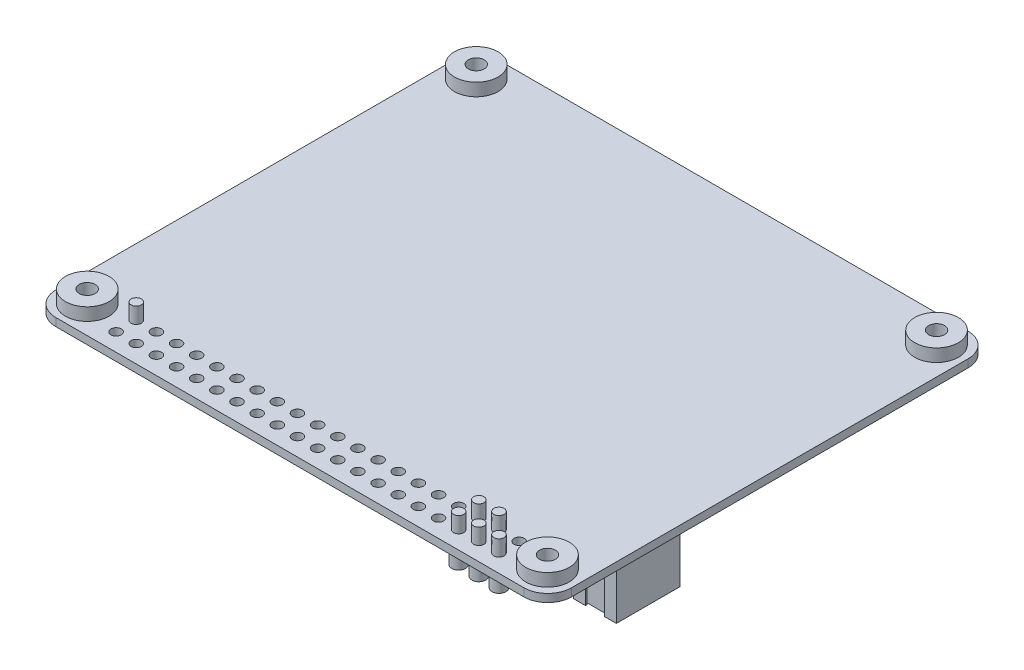
SolidWorks part; units mm, degrees
ref_plane "前视基准面" through (0, 0, 0) normal (0, 0, 1) x (1, 0, 0)
ref_plane "上视基准面" through (0, 0, 0) normal (0, 1, 0) x (1, 0, 0)
ref_plane "右视基准面" through (0, 0, 0) normal (1, 0, 0) x (0, 0, -1)
sketch "草图1" plane through (0, 0, 0) normal (0, 1, 0) x (1, 0, 0)
  line L1 (32.5, -28) -> (-32.5, -28)
  line L2 (32.5, -28) -> (32.5, 28)
  line L3 (32.5, 28) -> (-32.5, 28)
  line L4 (-32.5, -28) -> (-32.5, 28)
  line L5 (32.5, -28) -> (-32.5, 28) construction
  line L6 (32.5, 28) -> (-32.5, -28) construction
  point P0 (0, 0)
  dimension "D1" = 56
  dimension "D2" = 65
extrude "凸台-拉伸1" add sketch "草图1" along normal blind 1
fillet "圆角1" radius 3 4 edges at (32.5, 0.5, -28) (32.5, 0.5, 28) (-32.5, 0.5, 28) (-32.5, 0.5, -28)
sketch "草图2" plane through (0, 1, 0) normal (0, 1, 0) x (1, 0, 0)
  circle A0 centre (-29.0307, 24.5287) radius 2.75
  circle A1 centre (28.9808, 24.5287) radius 2.75
  circle A2 centre (-29.0307, -24.5065) radius 2.75
  circle A3 centre (28.9808, -24.5065) radius 2.75
  dimension "D1" = 5.5
extrude "凸台-拉伸2" add sketch "草图2" along normal blind 1.6
sketch "草图3" plane through (0, 2.6, 0) normal (0, 1, 0) x (1, 0, 0)
  circle A0 centre (-29.0307, 24.5287) radius 1
  circle A1 centre (28.9808, 24.5287) radius 1
  circle A2 centre (-29.0307, -24.5065) radius 1
  circle A3 centre (28.9808, -24.5065) radius 1
  dimension "D1" = 2
extrude "切除-拉伸1" cut sketch "草图3" against normal up to next
sketch "草图4" plane through (0, 0, 0) normal (0, -1, 0) x (1, 0, 0)
  line L0 (29.5, -28) -> (-29.5, -28) construction
  line L1 (25.5, -28) -> (16.5, -28)
  line L2 (25.5, -28) -> (25.5, -20.6)
  line L3 (25.5, -20.6) -> (16.5, -20.6)
  line L4 (16.5, -28) -> (16.5, -20.6)
  line L5 (32.5, 25) -> (32.5, -25) construction
  dimension "D1" = 7.4
  dimension "D2" = 9
  dimension "D3" = 7
extrude "凸台-拉伸3" add sketch "草图4" along normal blind 3.2
sketch "草图5" plane through (0, 0, -28) normal (0, 0, -1) x (-1, 0, 0)
  line L0 (-29.5, 0) -> (-25.5, 0) construction
  line L1 (-16.5, -3.2) -> (-25.5, -3.2)
  line L2 (-16.5, -3.2) -> (-16.5, 0)
  line L3 (-16.5, 0) -> (-25.5, 0)
  line L4 (-25.5, -3.2) -> (-25.5, 0)
  line L5 (-25.5, -3.2) -> (-25.5, 0) construction
extrude "凸台-拉伸4" add sketch "草图5" along normal blind 1
fillet "圆角3" radius 1 4 edges at (25.5, 0, -28.5) (25.5, -3.2, -24.8) (16.5, -3.2, -24.8) (16.5, 0, -28.5)
sketch "草图6" plane through (0, 0, 0) normal (0, -1, 0) x (1, 0, 0)
  line L0 (-32.5, -25) -> (-32.5, 25) construction
  circle A0 centre (-17.5, 0) radius 7
  dimension "D1" = 14
  dimension "D2" = 15
extrude "凸台-拉伸5" add sketch "草图6" along normal blind 2
sketch "草图8" plane through (0, 0, 0) normal (0, -1, 0) x (1, 0, 0)
  circle A0 centre (28.9808, 24.5065) radius 2
  circle A1 centre (28.9808, -24.5287) radius 2
  circle A2 centre (-29.0307, -24.5287) radius 2
  circle A3 centre (-29.0307, 24.5065) radius 2
  dimension "D1" = 4
extrude "凸台-拉伸6" add sketch "草图8" along normal blind 0.5
sketch "草图9" plane through (0, 0, 0) normal (0, 1, 0) x (1, 0, 0)
  circle A0 centre (-29.0307, 24.5287) radius 1
  circle A1 centre (28.9808, 24.5287) radius 1
  circle A2 centre (-29.0307, -24.5065) radius 1
  circle A3 centre (28.9808, -24.5065) radius 1
  circle A4 centre (28.9808, -24.5065) radius 2 construction
  circle A5 centre (28.9808, 24.5287) radius 2 construction
  circle A6 centre (-29.0307, -24.5065) radius 2 construction
  circle A7 centre (-29.0307, 24.5287) radius 2 construction
extrude "切除-拉伸2" cut sketch "草图9" against normal up to next
sketch "草图10" plane through (0, 0, -29) normal (0, 0, -1) x (-1, 0, 0)
  line L8 (-17.5, -0.2) -> (-24.5, -0.2)
  line L9 (-25.3, -1) -> (-25.3, -2.2)
  line L10 (-24.5, -3) -> (-17.5, -3)
  line L11 (-16.7, -2.2) -> (-16.7, -1)
  line L12 (-17.5, -0.2) -> (-24.5, -0.2)
  line L13 (-25.3, -1) -> (-25.3, -2.2)
  line L14 (-24.5, -3) -> (-17.5, -3)
  line L15 (-16.7, -2.2) -> (-16.7, -1)
  arc A8 (-24.5, -0.2) -> (-25.3, -1) centre (-24.5, -1) ccw
  arc A9 (-25.3, -2.2) -> (-24.5, -3) centre (-24.5, -2.2) ccw
  arc A10 (-17.5, -3) -> (-16.7, -2.2) centre (-17.5, -2.2) ccw
  arc A11 (-16.7, -1) -> (-17.5, -0.2) centre (-17.5, -1) ccw
  arc A12 (-24.5, -0.2) -> (-25.3, -1) centre (-24.5, -1) ccw
  arc A13 (-25.3, -2.2) -> (-24.5, -3) centre (-24.5, -2.2) ccw
  arc A14 (-17.5, -3) -> (-16.7, -2.2) centre (-17.5, -2.2) ccw
  arc A15 (-16.7, -1) -> (-17.5, -0.2) centre (-17.5, -1) ccw
  dimension "D1" = 0.2
extrude "切除-拉伸3" cut sketch "草图10" against normal blind 8
sketch "草图11" plane through (0, 0, 0) normal (0, -1, 0) x (1, 0, 0)
  line L0 (16.5, -28) -> (-29.5, -28) construction
  line L1 (6, -27.8) -> (10.5, -27.8)
  line L2 (6, -27.8) -> (6, -26.3)
  line L3 (6, -26.3) -> (10.5, -26.3)
  line L4 (10.5, -27.8) -> (10.5, -26.3)
  line L5 (16.5, -20.6) -> (16.5, -28) construction
  line L6 (-2.6793, -27.2) -> (-9.3793, -27.2)
  line L7 (-2.6793, -27.2) -> (-2.6793, -25)
  line L8 (-2.6793, -25) -> (-9.3793, -25)
  line L9 (-9.3793, -27.2) -> (-9.3793, -25)
  dimension "D1" = 6
  dimension "D2" = 4.5
  dimension "D3" = 6.7
  dimension "D4" = 0.8
  dimension "D5" = 2.2
  dimension "D6" = 1.5
  dimension "D7" = 8.7
  dimension "D8" = 0.2
extrude "凸台-拉伸7" add sketch "草图11" along normal blind 1.5
sketch "草图12" plane through (0, 0, 0) normal (0, -1, 0) x (1, 0, 0)
  line L0 (16.5, -28) -> (-29.5, -28) construction
  line L1 (-16.6, -28) -> (-23.9, -28)
  line L2 (-16.6, -28) -> (-16.6, -22.7)
  line L3 (-16.6, -22.7) -> (-23.9, -22.7)
  line L4 (-23.9, -28) -> (-23.9, -22.7)
  line L5 (-32.5, -25) -> (-32.5, 25) construction
  dimension "D1" = 7.3
  dimension "D2" = 8.6
  dimension "D3" = 5.3
extrude "凸台-拉伸8" add sketch "草图12" along normal blind 2.4
sketch "草图13" plane through (0, 0, -28) normal (0, 0, -1) x (-1, 0, 0)
  line L1 (23.9, -2.4) -> (16.6, -2.4)
  line L2 (23.9, -2.4) -> (23.9, 0)
  line L3 (23.9, 0) -> (16.6, 0)
  line L4 (16.6, -2.4) -> (16.6, 0)
extrude "凸台-拉伸9" add sketch "草图13" along normal up to surface (1 mm away) up to face at (21, -1.6, -29)
chamfer "倒角1" distance 0.4 angle 45 2 edges at (-16.6, -2.4, -25.85) (-23.9, -2.4, -25.85)
chamfer "倒角2" distance 1 angle 45 2 edges at (-16.6, 0, -28.5) (-23.9, 0, -28.5)
sketch "草图14" plane through (0, 0, -29) normal (0, 0, -1) x (-1, 0, 0)
  line L16 (22.8172, -0.2) -> (17.6828, -0.2)
  line L17 (17.6828, -0.2) -> (16.8, -1.0828)
  line L18 (16.8, -1.0828) -> (16.8, -1.9172)
  line L19 (16.8, -1.9172) -> (17.0828, -2.2)
  line L20 (17.0828, -2.2) -> (23.4172, -2.2)
  line L21 (23.4172, -2.2) -> (23.7, -1.9172)
  line L22 (23.7, -1.9172) -> (23.7, -1.0828)
  line L23 (23.7, -1.0828) -> (22.8172, -0.2)
  line L24 (22.8172, -0.2) -> (17.6828, -0.2)
  line L25 (17.6828, -0.2) -> (16.8, -1.0828)
  line L26 (16.8, -1.0828) -> (16.8, -1.9172)
  line L27 (16.8, -1.9172) -> (17.0828, -2.2)
  line L28 (17.0828, -2.2) -> (23.4172, -2.2)
  line L29 (23.4172, -2.2) -> (23.7, -1.9172)
  line L30 (23.7, -1.9172) -> (23.7, -1.0828)
  line L31 (23.7, -1.0828) -> (22.8172, -0.2)
  dimension "D1" = 0.2
extrude "切除-拉伸4" cut sketch "草图14" against normal blind 2.4
sketch "草图15" plane through (0, 0, -27.2) normal (0, 0, -1) x (-1, 0, 0)
  line L1 (6.6577, -1.3336) -> (5.7436, -1.3336)
  line L2 (6.6577, -1.3336) -> (6.6577, -0.2043)
  line L3 (6.6577, -0.2043) -> (5.7436, -0.2043)
  line L4 (5.7436, -1.3336) -> (5.7436, -0.2043)
extrude "凸台-拉伸10" add sketch "草图15" along normal blind 0.8
sketch "草图16" plane through (0, 0, -27.8) normal (0, 0, -1) x (-1, 0, 0)
  line L1 (-6.8432, -1.3088) -> (-8.9595, -1.3088)
  line L2 (-6.8432, -1.3088) -> (-6.8432, -0.1641)
  line L3 (-6.8432, -0.1641) -> (-8.9595, -0.1641)
  line L4 (-8.9595, -1.3088) -> (-8.9595, -0.1641)
extrude "凸台-拉伸11" add sketch "草图16" along normal blind 0.5
sketch "草图17" plane through (0, 0, -28) normal (0, 0, -1) x (-1, 0, 0)
  line L0 (23.9, -1) -> (23.9, 0)
  line L1 (23.9, 0) -> (22.9, 0)
  line L2 (22.9, 0) -> (23.9, -1)
  line L3 (16.6, 0) -> (17.6, 0)
  line L4 (17.6, 0) -> (16.6, -1)
  line L5 (16.6, -1) -> (16.6, 0) construction
  line L6 (16.6, -1) -> (16.6, 0)
extrude "切除-拉伸5" cut sketch "草图17" against normal up to surface (5.3 mm away) up to face at (-20.25, -1.4667, -22.7)
fillet "圆角4" radius 0.2 1 edges at (-17.5, -2, -7)
sketch "草图18" plane through (0, 0, 0) normal (0, -1, 0) x (1, 0, 0)
  line L0 (-29.5, 28) -> (29.5, 28) construction
  line L1 (27.1, 8.3) -> (20.1, 8.3)
  line L2 (27.1, 8.3) -> (27.1, 1.3)
  line L3 (27.1, 1.3) -> (20.1, 1.3)
  line L4 (20.1, 8.3) -> (20.1, 1.3)
  line L5 (27.1, -3.4) -> (20.1, -3.4)
  line L6 (27.1, -3.4) -> (27.1, -10.4)
  line L7 (27.1, -10.4) -> (20.1, -10.4)
  line L8 (20.1, -3.4) -> (20.1, -10.4)
  line L9 (32.5, 25) -> (32.5, -25) construction
  dimension "D1" = 7
  dimension "D2" = 19.7
  dimension "D3" = 4.7
  dimension "D4" = 5.4
extrude "凸台-拉伸12" add sketch "草图18" along normal blind 3
sketch "草图19" plane through (0, 0, 0) normal (0, -1, 0) x (1, 0, 0)
  line L0 (32.5, 25) -> (32.5, -25) construction
  line L1 (32, 18.85) -> (26.6, 18.85)
  line L2 (32, 18.85) -> (32, 10.85)
  line L3 (32, 10.85) -> (26.6, 10.85)
  line L4 (26.6, 18.85) -> (26.6, 10.85)
  line L5 (-29.5, 28) -> (29.5, 28) construction
  dimension "D1" = 8
  dimension "D2" = 5.4
  dimension "D3" = 0.5
  dimension "D4" = 9.15
extrude "凸台-拉伸13" add sketch "草图19" along normal blind 6.22
sketch "草图20" plane through (0, -6.22, 0) normal (0, -1, 0) x (1, 0, 0)
  line L0 (30.5, 18.85) -> (30.5, 18.65)
  line L1 (32, 18.85) -> (26.6, 18.85) construction
  line L2 (30.5, 18.65) -> (31.3599, 18.65)
  line L3 (31.3599, 18.65) -> (31.3599, 18.45)
  line L4 (31.3599, 18.45) -> (26.9378, 18.45)
  line L5 (26.9378, 18.45) -> (26.9378, 18.65)
  line L6 (26.9378, 18.65) -> (28.1, 18.65)
  line L7 (28.1, 18.65) -> (28.1, 18.85)
  line L8 (32, 18.85) -> (26.6, 18.85) construction
  line L9 (28.1, 18.85) -> (30.5, 18.85)
  line L10 (30.5, 10.85) -> (30.5, 11.05)
  line L11 (26.6, 10.85) -> (32, 10.85) construction
  line L12 (30.5, 11.05) -> (31.3599, 11.05)
  line L13 (31.3599, 11.05) -> (31.3599, 11.25)
  line L14 (31.3599, 11.25) -> (26.9378, 11.25)
  line L15 (26.9378, 11.25) -> (26.9378, 11.05)
  line L16 (26.9378, 11.05) -> (28.1, 11.05)
  line L17 (28.1, 11.05) -> (28.1, 10.85)
  line L18 (28.1, 10.85) -> (30.5, 10.85)
  line L19 (32, 10.85) -> (32, 18.85) construction
  line L20 (26.6, 18.85) -> (26.6, 10.85) construction
  dimension "D1" = 0.2
  dimension "D2" = 0.2
  dimension "D3" = 0.2
  dimension "D4" = 1.5
  dimension "D5" = 1.5
extrude "切除-拉伸6" cut sketch "草图20" against normal blind 6.22
sketch "草图21" plane through (0, -6.22, 0) normal (0, -1, 0) x (1, 0, 0)
  line L1 (31.3599, 18.0753) -> (26.9378, 18.0753)
  line L2 (31.3599, 18.0753) -> (31.3599, 11.6247)
  line L3 (31.3599, 11.6247) -> (26.9378, 11.6247)
  line L4 (26.9378, 18.0753) -> (26.9378, 11.6247)
  line L5 (31.3599, 18.0753) -> (26.9378, 11.6247) construction
  line L6 (31.3599, 11.6247) -> (26.9378, 18.0753) construction
  point P0 (29.1489, 14.85)
extrude "切除-拉伸7" cut sketch "草图21" against normal blind 5
sketch "草图22" plane through (0, -1.22, 0) normal (0, -1, 0) x (1, 0, 0)
  line L1 (29.5742, 16.0721) -> (29.0742, 16.0721)
  line L2 (29.5742, 16.0721) -> (29.5742, 15.5721)
  line L3 (29.5742, 15.5721) -> (29.0742, 15.5721)
  line L4 (29.0742, 16.0721) -> (29.0742, 15.5721)
  line L5 (29.5742, 16.0721) -> (29.0742, 15.5721) construction
  line L6 (29.5742, 15.5721) -> (29.0742, 16.0721) construction
  line L7 (29.5566, 14.331) -> (29.0566, 14.331)
  line L8 (29.5566, 14.331) -> (29.5566, 13.831)
  line L9 (29.5566, 13.831) -> (29.0566, 13.831)
  line L10 (29.0566, 14.331) -> (29.0566, 13.831)
  line L11 (29.5566, 14.331) -> (29.0566, 13.831) construction
  line L12 (29.5566, 13.831) -> (29.0566, 14.331) construction
  point P0 (29.3242, 15.8221)
  point P5 (29.3066, 14.081)
  dimension "D1" = 0.5
extrude "凸台-拉伸14" add sketch "草图22" along normal blind 5
chamfer "倒角3" distance 0.1 angle 45 8 edges at (29.3066, -6.22, 14.331) (29.5566, -6.22, 14.081) (29.3066, -6.22, 13.831) (29.0566, -6.22, 14.081) (29.3242, -6.22, 16.0721) (29.5742, -6.22, 15.8221) (29.3242, -6.22, 15.5721) (29.0742, -6.22, 15.8221)
sketch "草图23" plane through (0, 0, 0) normal (0, -1, 0) x (1, 0, 0)
  circle A0 centre (12.8757, -15.76) radius 3.3198
extrude "凸台-拉伸15" add sketch "草图23" along normal blind 1.5
sketch "草图24" plane through (0, 0, 0) normal (0, -1, 0) x (1, 0, 0)
  line L1 (18.7716, 11.9855) -> (16.6907, 11.9855)
  line L2 (18.7716, 11.9855) -> (18.7716, 7.4768)
  line L3 (18.7716, 7.4768) -> (16.6907, 7.4768)
  line L4 (16.6907, 11.9855) -> (16.6907, 7.4768)
  line L5 (18.7716, 11.9855) -> (16.6907, 7.4768) construction
  line L6 (18.7716, 7.4768) -> (16.6907, 11.9855) construction
  line L7 (18.7716, 5.3092) -> (16.6907, 5.3092)
  line L8 (18.7716, 5.3092) -> (18.7716, 0.974)
  line L9 (18.7716, 0.974) -> (16.6907, 0.974)
  line L10 (16.6907, 5.3092) -> (16.6907, 0.974)
  line L11 (18.7716, 5.3092) -> (16.6907, 0.974) construction
  line L12 (18.7716, 0.974) -> (16.6907, 5.3092) construction
  line L13 (15.6772, -1.762) -> (10.6483, -1.762)
  line L14 (15.6772, -1.762) -> (15.6772, -7.762)
  line L15 (15.6772, -7.762) -> (10.6483, -7.762)
  line L16 (10.6483, -1.762) -> (10.6483, -7.762)
  line L17 (15.6772, -1.762) -> (10.6483, -7.762) construction
  line L18 (15.6772, -7.762) -> (10.6483, -1.762) construction
  point P0 (17.7311, 9.7312)
  point P5 (17.7311, 3.1416)
  point P10 (13.1628, -4.762)
  dimension "D1" = 6
extrude "凸台-拉伸16" add sketch "草图24" along normal blind 1.5
sketch "草图25" plane through (0, 0, 0) normal (0, -1, 0) x (1, 0, 0)
  line L1 (15.1967, 7.9079) -> (11.1314, 7.9079)
  line L2 (15.1967, 7.9079) -> (15.1967, 3.8427)
  line L3 (15.1967, 3.8427) -> (11.1314, 3.8427)
  line L4 (11.1314, 7.9079) -> (11.1314, 3.8427)
  line L5 (15.1967, 7.9079) -> (11.1314, 3.8427) construction
  line L6 (15.1967, 3.8427) -> (11.1314, 7.9079) construction
  line L7 (21.5006, 15.4932) -> (19.7006, 15.4932)
  line L8 (21.5006, 15.4932) -> (21.5006, 14.4025)
  line L9 (21.5006, 14.4025) -> (19.7006, 14.4025)
  line L10 (19.7006, 15.4932) -> (19.7006, 14.4025)
  line L11 (21.5006, 15.4932) -> (19.7006, 14.4025) construction
  line L12 (21.5006, 14.4025) -> (19.7006, 15.4932) construction
  line L13 (21.5006, 13.6588) -> (19.7006, 13.6588)
  line L14 (21.5006, 13.6588) -> (21.5006, 12.5682)
  line L15 (21.5006, 12.5682) -> (19.7006, 12.5682)
  line L16 (19.7006, 13.6588) -> (19.7006, 12.5682)
  line L17 (21.5006, 13.6588) -> (19.7006, 12.5682) construction
  line L18 (21.5006, 12.5682) -> (19.7006, 13.6588) construction
  line L19 (21.5006, 11.8741) -> (19.7006, 11.8741)
  line L20 (21.5006, 11.8741) -> (21.5006, 10.7834)
  line L21 (21.5006, 10.7834) -> (19.7006, 10.7834)
  line L22 (19.7006, 11.8741) -> (19.7006, 10.7834)
  line L23 (21.5006, 11.8741) -> (19.7006, 10.7834) construction
  line L24 (21.5006, 10.7834) -> (19.7006, 11.8741) construction
  line L25 (18.7662, 14.8563) -> (17.6756, 14.8563)
  line L26 (18.7662, 14.8563) -> (18.7662, 13.0563)
  line L27 (18.7662, 13.0563) -> (17.6756, 13.0563)
  line L28 (17.6756, 14.8563) -> (17.6756, 13.0563)
  line L29 (18.7662, 14.8563) -> (17.6756, 13.0563) construction
  line L30 (18.7662, 13.0563) -> (17.6756, 14.8563) construction
  line L31 (16.9319, 14.8563) -> (15.8412, 14.8563)
  line L32 (16.9319, 14.8563) -> (16.9319, 13.0563)
  line L33 (16.9319, 13.0563) -> (15.8412, 13.0563)
  line L34 (15.8412, 14.8563) -> (15.8412, 13.0563)
  line L35 (16.9319, 14.8563) -> (15.8412, 13.0563) construction
  line L36 (16.9319, 13.0563) -> (15.8412, 14.8563) construction
  line L37 (15.0976, 14.8563) -> (14.0069, 14.8563)
  line L38 (15.0976, 14.8563) -> (15.0976, 13.0563)
  line L39 (15.0976, 13.0563) -> (14.0069, 13.0563)
  line L40 (14.0069, 14.8563) -> (14.0069, 13.0563)
  line L41 (15.0976, 14.8563) -> (14.0069, 13.0563) construction
  line L42 (15.0976, 13.0563) -> (14.0069, 14.8563) construction
  line L43 (13.2632, 14.8563) -> (12.1725, 14.8563)
  line L44 (13.2632, 14.8563) -> (13.2632, 13.0563)
  line L45 (13.2632, 13.0563) -> (12.1725, 13.0563)
  line L46 (12.1725, 14.8563) -> (12.1725, 13.0563)
  line L47 (13.2632, 14.8563) -> (12.1725, 13.0563) construction
  line L48 (13.2632, 13.0563) -> (12.1725, 14.8563) construction
  line L49 (11.3297, 14.8563) -> (10.2391, 14.8563)
  line L50 (11.3297, 14.8563) -> (11.3297, 13.0563)
  line L51 (11.3297, 13.0563) -> (10.2391, 13.0563)
  line L52 (10.2391, 14.8563) -> (10.2391, 13.0563)
  line L53 (11.3297, 14.8563) -> (10.2391, 13.0563) construction
  line L54 (11.3297, 13.0563) -> (10.2391, 14.8563) construction
  line L55 (9.2971, 14.8563) -> (8.2064, 14.8563)
  line L56 (9.2971, 14.8563) -> (9.2971, 13.0563)
  line L57 (9.2971, 13.0563) -> (8.2064, 13.0563)
  line L58 (8.2064, 14.8563) -> (8.2064, 13.0563)
  line L59 (9.2971, 14.8563) -> (8.2064, 13.0563) construction
  line L60 (9.2971, 13.0563) -> (8.2064, 14.8563) construction
  point P0 (13.1641, 5.8753)
  point P5 (20.6006, 14.9478)
  point P10 (20.6006, 13.1135)
  point P15 (20.6006, 11.3287)
  point P20 (18.2209, 13.9563)
  point P25 (16.3866, 13.9563)
  point P30 (14.5522, 13.9563)
  point P35 (12.7179, 13.9563)
  point P40 (10.7844, 13.9563)
  point P45 (8.7518, 13.9563)
  dimension "D1" = 1.8
extrude "凸台-拉伸17" add sketch "草图25" along normal blind 1
sketch "草图26" plane through (0, 0, 0) normal (0, -1, 0) x (1, 0, 0)
  circle A0 centre (24.13, 25.77) radius 0.65
  circle A40 centre (21.59, 25.77) radius 0.65
  circle A41 centre (19.05, 25.77) radius 0.65
  circle A42 centre (16.51, 25.77) radius 0.65
  circle A43 centre (13.97, 25.77) radius 0.65
  circle A44 centre (11.43, 25.77) radius 0.65
  circle A45 centre (8.89, 25.77) radius 0.65
  circle A46 centre (6.35, 25.77) radius 0.65
  circle A47 centre (3.81, 25.77) radius 0.65
  circle A48 centre (1.27, 25.77) radius 0.65
  circle A49 centre (-1.27, 25.77) radius 0.65
  circle A50 centre (-3.81, 25.77) radius 0.65
  circle A51 centre (-6.35, 25.77) radius 0.65
  circle A52 centre (-8.89, 25.77) radius 0.65
  circle A53 centre (-11.43, 25.77) radius 0.65
  circle A54 centre (-13.97, 25.77) radius 0.65
  circle A55 centre (-16.51, 25.77) radius 0.65
  circle A56 centre (-19.05, 25.77) radius 0.65
  circle A57 centre (-21.59, 25.77) radius 0.65
  circle A58 centre (-24.13, 25.77) radius 0.65
  circle A59 centre (21.59, 23.23) radius 0.65
  circle A60 centre (19.05, 23.23) radius 0.65
  circle A61 centre (16.51, 23.23) radius 0.65
  circle A62 centre (13.97, 23.23) radius 0.65
  circle A63 centre (11.43, 23.23) radius 0.65
  circle A64 centre (8.89, 23.23) radius 0.65
  circle A65 centre (6.35, 23.23) radius 0.65
  circle A66 centre (3.81, 23.23) radius 0.65
  circle A67 centre (1.27, 23.23) radius 0.65
  circle A68 centre (-1.27, 23.23) radius 0.65
  circle A69 centre (-3.81, 23.23) radius 0.65
  circle A70 centre (-6.35, 23.23) radius 0.65
  circle A71 centre (-8.89, 23.23) radius 0.65
  circle A72 centre (-11.43, 23.23) radius 0.65
  circle A73 centre (-13.97, 23.23) radius 0.65
  circle A74 centre (-16.51, 23.23) radius 0.65
  circle A75 centre (-19.05, 23.23) radius 0.65
  circle A76 centre (-21.59, 23.23) radius 0.65
  circle A77 centre (-24.13, 23.23) radius 0.65
  circle A78 centre (24.13, 23.23) radius 0.65
  dimension "D1" = 1.3
  dimension "D2" = 20
  dimension "D3" = 2
extrude "切除-拉伸8" cut sketch "草图26" against normal up to surface (1 mm away) up to face at (28.9808, 1, 27.2565)
sketch "草图27" plane through (0, 0, 0) normal (0, -1, 0) x (1, 0, 0)
  circle A0 centre (24.13, 25.77) radius 1.15
  circle A1 centre (21.59, 25.77) radius 1.15
  circle A2 centre (21.59, 23.23) radius 1.15
  circle A3 centre (19.05, 25.77) radius 1.15
  circle A4 centre (19.05, 23.23) radius 1.15
  circle A5 centre (-24.13, 23.23) radius 1.15
  circle A6 centre (21.59, 25.77) radius 0.65 construction
  dimension "D1" = 2.3
extrude "凸台-拉伸18" add sketch "草图27" along normal blind 0.8
sketch "草图28" plane through (0, -0.8, 0) normal (0, -1, 0) x (-1, 0, 0)
  circle A0 centre (-24.13, -25.77) radius 0.875
  circle A1 centre (-21.59, -25.77) radius 0.875
  circle A2 centre (-19.05, -23.23) radius 0.875
  circle A3 centre (-21.59, -23.23) radius 0.875
  circle A4 centre (-19.05, -25.77) radius 0.875
  circle A5 centre (24.13, -23.23) radius 0.875
  dimension "D1" = 1.75
extrude "凸台-拉伸19" add sketch "草图28" along normal blind 2
sketch "草图29" plane through (0, 0, 0) normal (0, 1, 0) x (1, 0, 0)
  circle A0 centre (19.05, -23.23) radius 0.65 construction
  circle A1 centre (19.05, -25.77) radius 0.65 construction
  circle A2 centre (21.59, -23.23) radius 0.65 construction
  circle A4 centre (24.13, -25.77) radius 0.65 construction
  circle A5 centre (-24.13, -23.23) radius 0.65 construction
  circle A6 centre (19.05, -23.23) radius 0.65
  circle A7 centre (19.05, -25.77) radius 0.65
  circle A8 centre (21.59, -23.23) radius 0.65
  circle A9 centre (21.59, -25.77) radius 0.65
  circle A10 centre (24.13, -25.77) radius 0.65
  circle A11 centre (-24.13, -23.23) radius 0.65
  circle A12 centre (21.59, -25.77) radius 0.65 construction
extrude "凸台-拉伸20" add sketch "草图29" along normal blind 3
sketch "草图30" plane through (0, 0, 0) normal (0, -1, 0) x (1, 0, 0)
  line L1 (-0.3871, -24.7121) -> (2.6129, -24.7121)
  line L2 (-0.3871, -24.7121) -> (-0.3871, -27.7121)
  line L3 (-0.3871, -27.7121) -> (2.6129, -27.7121)
  line L4 (2.6129, -24.7121) -> (2.6129, -27.7121)
  line L5 (-0.3871, -24.7121) -> (2.6129, -27.7121) construction
  line L6 (-0.3871, -27.7121) -> (2.6129, -24.7121) construction
  point P0 (1.1129, -26.2121)
  dimension "D1" = 3
  dimension "D2" = 3
extrude "凸台-拉伸21" add sketch "草图30" along normal blind 1
sketch "草图31" plane through (0, -1, 0) normal (0, -1, 0) x (1, 0, 0)
  line L0 (2.6129, -27.7121) -> (2.6129, -24.7121) construction
  line L1 (-0.3871, -27.7121) -> (2.6129, -27.7121) construction
  circle A0 centre (1.1129, -26.2121) radius 1
  point P5 (2.6129, -26.2121)
  point P8 (1.1129, -27.7121)
  dimension "D1" = 2
extrude "凸台-拉伸22" add sketch "草图31" along normal blind 0.6
chamfer "倒角4" distance 0.4 angle 45 4 edges at (2.6129, -0.5, -24.7121) (-0.3871, -0.5, -24.7121) (2.6129, -0.5, -27.7121) (-0.3871, -0.5, -27.7121)
